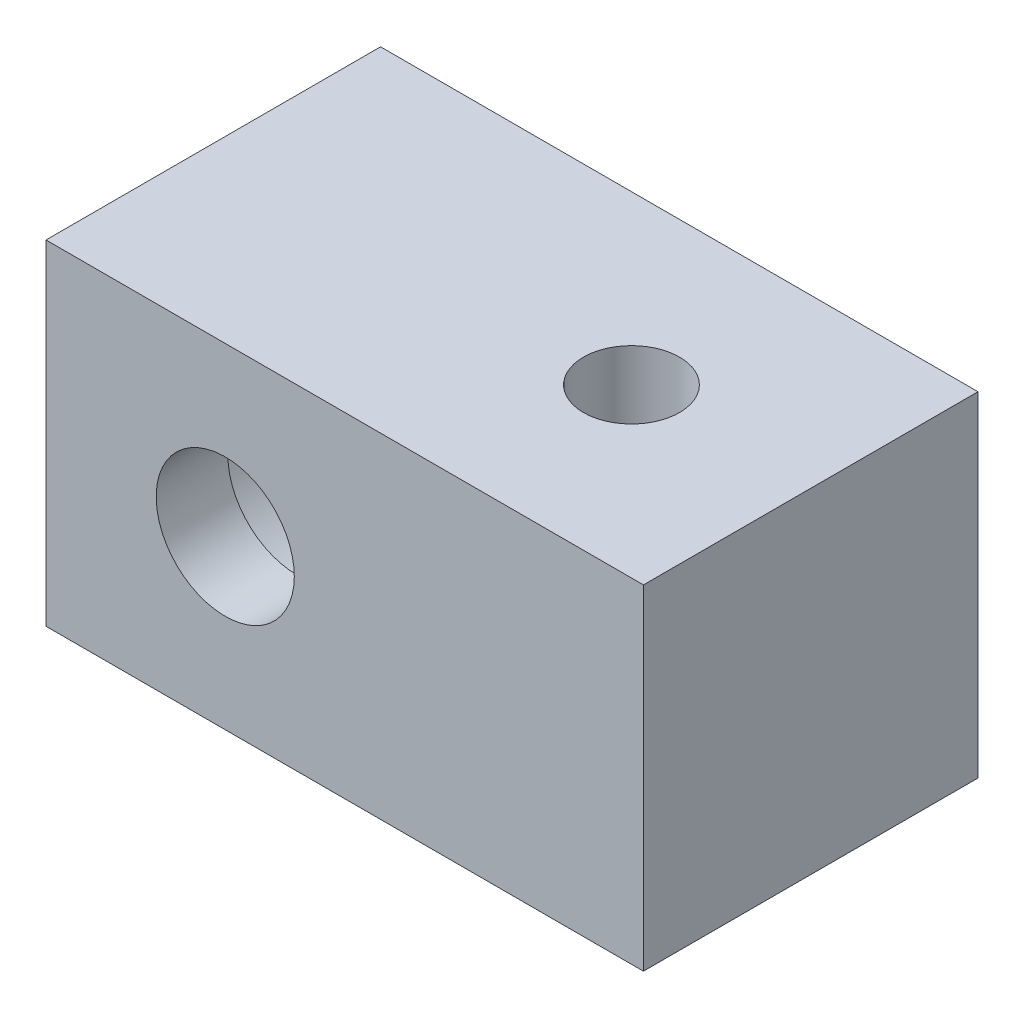
SolidWorks part; units mm, degrees
ref_plane "Front Plane" through (0, 0, 0) normal (0, 0, 1) x (1, 0, 0)
ref_plane "Top Plane" through (0, 0, 0) normal (0, 1, 0) x (1, 0, 0)
ref_plane "Right Plane" through (0, 0, 0) normal (1, 0, 0) x (0, 0, -1)
sketch "Sketch1" plane through (0, 0, 0) normal (0, 1, 0) x (1, 0, 0)
  line L1 (-15.875, 8.89) -> (15.875, 8.89)
  line L2 (-15.875, 8.89) -> (-15.875, -8.89)
  line L3 (-15.875, -8.89) -> (15.875, -8.89)
  line L4 (15.875, 8.89) -> (15.875, -8.89)
  line L5 (-15.875, 8.89) -> (15.875, -8.89) construction
  line L6 (-15.875, -8.89) -> (15.875, 8.89) construction
  point P0 (0, 0)
  dimension "D1" = 17.78
  dimension "D2" = 31.75
extrude "Boss-Extrude1" add sketch "Sketch1" along normal blind 17.78
sketch "Sketch2" plane through (0, 0, 8.89) normal (0, 0, 1) x (1, 0, 0)
  line L0 (-15.875, 8.89) -> (15.875, 8.89) construction
  line L1 (-15.875, 17.78) -> (-15.875, 0) construction
  line L2 (15.875, 17.78) -> (15.875, 0) construction
  line L3 (0, 17.78) -> (0, 0) construction
  line L4 (-15.875, 17.78) -> (15.875, 17.78) construction
  circle A0 centre (-6.35, 8.89) radius 3.6703
  dimension "D1" = 7.3406
  dimension "D2" = 6.35
sketch "Sketch3" plane through (0, 0, -8.89) normal (0, 0, -1) x (-1, 0, 0)
  circle A0 centre (6.35, 8.89) radius 6.4389
  dimension "D1" = 12.8778
extrude "Cut-Extrude1" cut sketch "Sketch3" against normal blind 13.97
extrude "Cut-Extrude2" cut sketch "Sketch2" against normal up to next
hole_wizard "1/4-20 Tapped Hole1" positions "Sketch5" profile "Sketch6" tap size "1/4-20" standard "ANSI Inch" end condition through all
sketch "Sketch5" plane through (0, 17.78, 0) normal (0, 1, 0) x (1, 0, 0)
  line L0 (-15.875, 0) -> (15.875, 0) construction
  line L1 (-15.875, 8.89) -> (-15.875, -8.89) construction
  line L2 (15.875, -8.89) -> (15.875, 8.89) construction
  point P8 (6.35, 0)
  dimension "D1" = 6.35
sketch "Sketch6" plane through (6.35, 17.78, 0) normal (1, 0, 0) x (0, 0, 1)
  line L0 (0, 0) -> (0, 17.78)
  line L1 (0, 17.78) -> (2.5527, 17.78)
  line L2 (2.5527, 17.78) -> (2.5527, 0)
  line L5 (2.5527, 0) -> (0, 0)
  line L11 (0, -6.35) -> (0, 107.95) construction
  dimension "Thru Tap Drill Dia." = 5.1054
  dimension "Thru Tap Drill Depth" = 17.78
cosmetic thread "Hole Thread1" parameters "D2"=6.35
